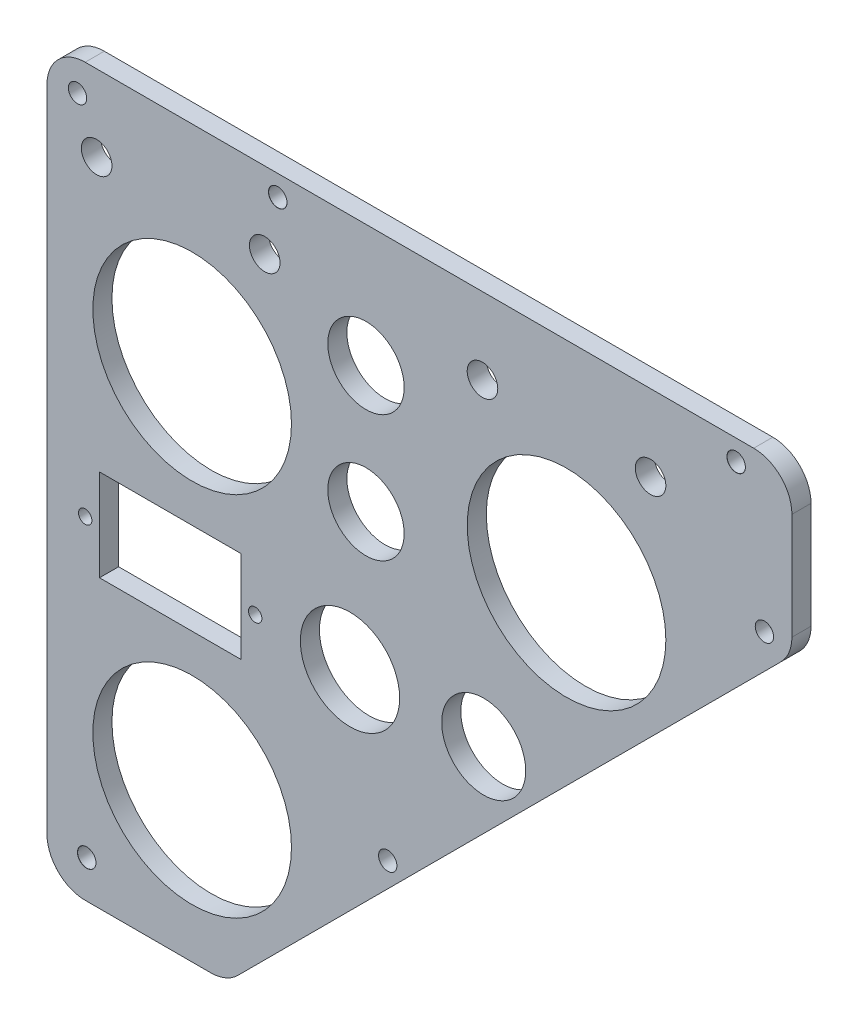
SolidWorks part; units mm, degrees
ref_plane "Piano frontale" through (0, 0, 0) normal (0, 0, 1) x (1, 0, 0)
ref_plane "Piano superiore" through (0, 0, 0) normal (0, 1, 0) x (1, 0, 0)
ref_plane "Piano destro" through (0, 0, 0) normal (1, 0, 0) x (0, 0, -1)
sketch "Schizzo1" plane through (0, 0, 0) normal (0, 0, 1) x (1, 0, 0)
  line L0 (0, 10) -> (0, 180)
  line L1 (10, 190) -> (185, 190)
  line L2 (195, 180) -> (195, 152.1421)
  line L3 (192.0711, 145.0711) -> (49.9289, 2.9289)
  line L4 (42.8579, 0) -> (10, 0)
  arc A0 (0, 180) -> (10, 190) centre (10, 180) cw
  arc A1 (0, 10) -> (10, 0) centre (10, 10) ccw
  arc A2 (49.9289, 2.9289) -> (42.8579, 0) centre (42.8579, 10) cw
  arc A3 (195, 152.1421) -> (192.0711, 145.0711) centre (185, 152.1421) cw
  arc A4 (185, 190) -> (195, 180) centre (185, 180) cw
  point P8 (0, 190)
  point P11 (0, 0)
  point P14 (47, 0)
  point P17 (195, 148)
  point P20 (195, 190)
  dimension "D5" = 10
  dimension "D1" = 195
  dimension "D2" = 42
  dimension "D3" = 45
  dimension "D4" = 190
extrude "Estrusione-Estrusione1" add sketch "Schizzo1" along normal blind 5
hole_wizard "Foro per Vite M4-2" positions "Schizzo3" profile "Schizzo4" hole size "M4" standard "ISO" end condition through all
sketch "Schizzo3" plane through (0, 0, 5) normal (0, 0, 1) x (1, 0, 0)
  line L2 (185, 190) -> (10, 190) construction
  line L4 (0, 180) -> (0, 10) construction
  point P0 (60.4, 184.6)
  point P2 (10.4, 9.89)
  point P10 (180.4, 184.6)
  dimension "D1" = 5.4
  dimension "D2" = 180.11
  dimension "D3" = 60.4
  dimension "D4" = 120
  dimension "D5" = 10.4
sketch "Schizzo4" plane through (60.4, 184.6, 5) normal (1, 0, 0) x (0, -1, 0)
  line L0 (0, 0) -> (0, 5)
  line L1 (0, 5) -> (2.4, 5)
  line L2 (2.4, 5) -> (2.4, 0.025)
  line L3 (2.4, 0.025) -> (2.425, 0)
  line L5 (2.425, 0) -> (0, 0)
  line L6 (-2.4, 0.025) -> (-2.425, 0) construction
  line L11 (0, -6.35) -> (0, 107.95) construction
  dimension "Thru Hole Dia." = 4.8
  dimension "Thru Hole Depth" = 5
  dimension "Near C'Sink Dia." = 4.85
  dimension "Near C'Sink Angle" = 90
sketch "Schizzo5" plane through (0, 0, 5) normal (0, 0, 1) x (1, 0, 0)
  line L0 (13.75, 75) -> (13.75, 99)
  line L1 (50.75, 75) -> (13.75, 75)
  line L2 (50.75, 99) -> (50.75, 75)
  line L3 (13.75, 99) -> (50.75, 99)
  line L4 (185, 190) -> (10, 190) construction
  line L5 (195, 152.1421) -> (195, 180) construction
  line L6 (0, 180) -> (0, 10) construction
  line L7 (83.5, 158) -> (83.5, 124.8501) construction
  circle A1 centre (10, 87) radius 1.75
  circle A2 centre (54.5, 87) radius 1.75
  circle A3 centre (83.5, 158) radius 10
  circle A4 centre (114.3195, 87) radius 11
  circle A5 centre (79.3195, 87) radius 13
  circle A15 centre (10.4, 9.89) radius 2.25 construction
  circle A16 centre (10.4, 9.89) radius 2.25 construction
  circle A17 centre (38, 135) radius 26
  circle A18 centre (136, 135) radius 26
  circle A19 centre (38, 39) radius 26
  circle A20 centre (83.5, 124.8501) radius 10
  point P17 (13.75, 87)
  dimension "D4" = 32
  dimension "D7" = 80.6805
  dimension "interruttore" = 20
  dimension "D16" = 24
  dimension "D17" = 38
  dimension "D6" = 26
  dimension "D10" = 52
  dimension "D20" = 3.5
  dimension "D27" = 20
  dimension "D3" = 22
  dimension "D5" = 35
  dimension "D8" = 55
  dimension "D9" = 98
  dimension "D11" = 96
  dimension "D12" = 52.5
  dimension "D13" = 37
  dimension "D14" = 3.75
  dimension "D15" = 3.75
  dimension "D18" = 48
  dimension "D19" = 10
  dimension "D25" = 33.1499
extrude "Taglio-Estrusione2" cut sketch "Schizzo5" against normal blind 7
sketch "Schizzo6" plane through (0, 0, 5) normal (0, 0, 1) x (1, 0, 0)
  circle A0 centre (13, 170) radius 4
  circle A1 centre (57, 170) radius 4
  circle A2 centre (114, 170) radius 4
  circle A3 centre (158, 170) radius 4
  circle A4 centre (38, 135) radius 26 construction
  circle A5 centre (136, 135) radius 26 construction
  dimension "D1" = 8
  dimension "D2" = 25
  dimension "D5" = 22
  dimension "D3" = 44
  dimension "D4" = 35
  dimension "D6" = 44
extrude "Taglio-Estrusione3" cut sketch "Schizzo6" against normal blind 10
hole_wizard "Foro per Vite M4-1" positions "Schizzo9" profile "Schizzo10" hole size "M4" standard "ISO"
sketch "Schizzo9" plane through (0, 0, 0) normal (0, 0, -1) x (-1, 0, 0)
  line L0 (-185, 190) -> (-10, 190) construction
  line L1 (0, 180) -> (0, 10) construction
  line L2 (-195, 152.1421) -> (-195, 180) construction
  point P0 (-187.8, 149.8191)
  point P2 (-8, 182)
  point P15 (-89.1939, 48.6)
  dimension "D1" = 8
  dimension "D2" = 8
  dimension "D3" = 7.2
  dimension "D4" = 40.1809
  dimension "D5" = 48.6
  dimension "D6" = 89.1939
sketch "Schizzo10" plane through (187.8, 149.8191, 0) normal (1, 0, 0) x (0, 1, 0)
  line L0 (0, 0) -> (0, 42.0421)
  line L1 (0, 42.0421) -> (2.4, 40.6)
  line L2 (2.4, 40.6) -> (2.4, 1.625)
  line L3 (2.4, 1.625) -> (4.025, 0)
  line L5 (4.025, 0) -> (0, 0)
  line L6 (-2.4, 1.625) -> (-4.025, 0) construction
  line L10 (0, 42.0421) -> (-2.4, 40.6) construction
  line L11 (0, -6.35) -> (0, 107.95) construction
  dimension "Hole Dia." = 4.8
  dimension "Hole Depth" = 40.6
  dimension "Near C'Sink Dia." = 8.05
  dimension "Near C'Sink Angle" = 90
  dimension "Drill Angle" = 118
